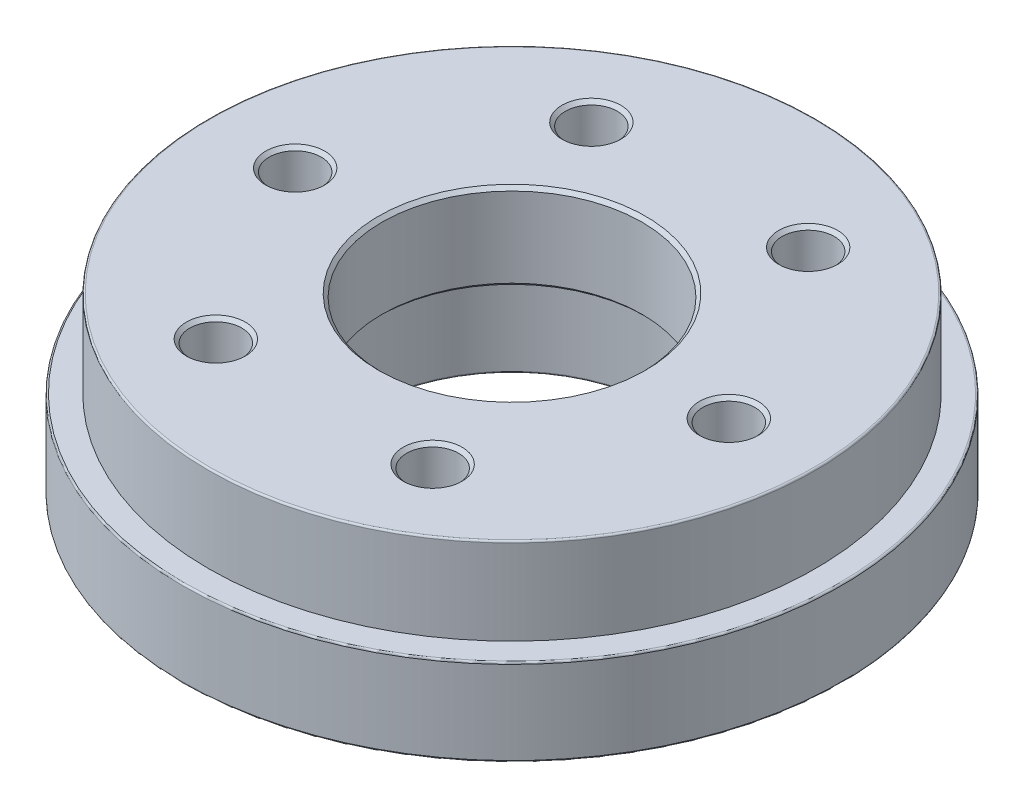
SolidWorks part; units mm, degrees
ref_plane "前视基准面" through (0, 0, 0) normal (0, 0, 1) x (1, 0, 0)
ref_plane "上视基准面" through (0, 0, 0) normal (0, 1, 0) x (1, 0, 0)
ref_plane "右视基准面" through (0, 0, 0) normal (1, 0, 0) x (0, 0, -1)
other "Configuration Table"
sketch "草图1" plane through (0, 0, 0) normal (0, 1, 0) x (1, 0, 0)
  circle A0 centre (0, 0) radius 19
  circle A1 centre (0, 0) radius 15 construction
  circle A2 centre (0, 15) radius 3.05
  circle A3 centre (12.9904, 7.5) radius 3.05
  circle A4 centre (12.9904, -7.5) radius 3.05
  circle A5 centre (0, -15) radius 3.05
  circle A6 centre (-12.9904, -7.5) radius 3.05
  circle A7 centre (-12.9904, 7.5) radius 3.05
  point P18 (0, 0)
  dimension "D1" = 6.1
  dimension "D2" = 38
  dimension "D3" = 30
  dimension "D4" = 6
extrude "凸台-拉伸1" add sketch "草图1" along normal blind 5 contours A0
extrude "切除-拉伸1" cut sketch "草图1<3>" along normal blind 4 contours A7 | A6 | A5 | A4 | A3 | A2 region at (0, 0, -15) region at (12.9904, 0, -7.5) region at (12.9904, 0, 7.5) region at (0, 0, 15) region at (-12.9904, 0, 7.5) region at (-12.9904, 0, -7.5)
sketch "草图1<3>" plane through (0, 0, 0) normal (0, 1, 0) x (1, 0, 0) same geometry as "草图1"
sketch "草图5" plane through (0, 5, 0) normal (0, 1, 0) x (1, 0, 0)
  circle A1 centre (0, 0) radius 17.5
  dimension "D1" = 35
extrude "凸台-拉伸3" add sketch "草图5" along normal blind 5
sketch "草图7" plane through (0, 0, 0) normal (0, -1, 0) x (1, 0, 0)
  circle A0 centre (0, 0) radius 8.5
  dimension "D1" = 17
extrude "切除-拉伸2" cut sketch "草图7" against normal blind 5
sketch "草图8" plane through (0, 5, 0) normal (0, -1, 0) x (1, 0, 0)
  circle A0 centre (0, 0) radius 7.5
  dimension "D1" = 15
extrude "切除-拉伸3" cut sketch "草图8" against normal blind 0.5
sketch "草图10" plane through (0, 0, 0) normal (0, -1, 0) x (1, 0, 0)
  line L0 (0, 15) -> (12.9904, 7.5) construction
  line L2 (6.25, 10.8253) -> (0, 0) construction
  circle A0 centre (0, 0) radius 12.5 construction
  circle A1 centre (6.25, 10.8253) radius 1.5
  circle A2 centre (12.5, 0) radius 1.5
  circle A3 centre (6.25, -10.8253) radius 1.5
  circle A4 centre (-6.25, -10.8253) radius 1.5
  circle A5 centre (-12.5, 0) radius 1.5
  circle A6 centre (-6.25, 10.8253) radius 1.5
  point P21 (0, 0)
  dimension "D1" = 3
  dimension "D3" = 25
  dimension "D2" = 6
extrude "切除-拉伸4" cut sketch "草图10" against normal up to next
sketch "草图11" plane through (0, 0, 0) normal (0, -1, 0) x (1, 0, 0)
  line L0 (6.25, -14.0007) -> (9, -12.413)
  line L1 (15.25, -1.5877) -> (15.25, 1.5877)
  line L2 (15.25, 1.5877) -> (12.5, 3.1754)
  line L3 (12.5, 3.1754) -> (9.75, 1.5877)
  line L4 (9.75, 1.5877) -> (9.75, -1.5877)
  line L5 (9.75, -1.5877) -> (12.5, -3.1754)
  line L6 (12.5, -3.1754) -> (15.25, -1.5877)
  line L7 (9, -12.413) -> (9, -9.2376)
  line L8 (9, -9.2376) -> (6.25, -7.6499)
  line L9 (6.25, -7.6499) -> (3.5, -9.2376)
  line L10 (3.5, -9.2376) -> (3.5, -12.413)
  line L11 (3.5, -12.413) -> (6.25, -14.0007)
  line L12 (-9, -12.413) -> (-6.25, -14.0007)
  line L13 (-6.25, -14.0007) -> (-3.5, -12.413)
  line L14 (-3.5, -12.413) -> (-3.5, -9.2376)
  line L15 (-3.5, -9.2376) -> (-6.25, -7.6499)
  line L16 (-6.25, -7.6499) -> (-9, -9.2376)
  line L17 (-9, -9.2376) -> (-9, -12.413)
  line L18 (-15.25, 1.5877) -> (-15.25, -1.5877)
  line L19 (-15.25, -1.5877) -> (-12.5, -3.1754)
  line L20 (-12.5, -3.1754) -> (-9.75, -1.5877)
  line L21 (-9.75, -1.5877) -> (-9.75, 1.5877)
  line L22 (-9.75, 1.5877) -> (-12.5, 3.1754)
  line L23 (-12.5, 3.1754) -> (-15.25, 1.5877)
  line L24 (-6.25, 14.0007) -> (-9, 12.413)
  line L25 (-9, 12.413) -> (-9, 9.2376)
  line L26 (-9, 9.2376) -> (-6.25, 7.6499)
  line L27 (-6.25, 7.6499) -> (-3.5, 9.2376)
  line L28 (-3.5, 9.2376) -> (-3.5, 12.413)
  line L29 (-3.5, 12.413) -> (-6.25, 14.0007)
  line L30 (9, 12.413) -> (6.25, 14.0007)
  line L31 (6.25, 14.0007) -> (3.5, 12.413)
  line L32 (3.5, 12.413) -> (3.5, 9.2376)
  line L33 (3.5, 9.2376) -> (6.25, 7.6499)
  line L34 (6.25, 7.6499) -> (9, 9.2376)
  line L35 (9, 9.2376) -> (9, 12.413)
  circle A0 centre (12.5, 0) radius 2.75 construction
  point P41 (0, 0)
  dimension "D1" = 5.5
  dimension "D2" = 6
extrude "切除-拉伸5" cut sketch "草图11" against normal blind 2
sketch "草图12" plane through (0, 10, 0) normal (0, 1, 0) x (1, 0, 0)
  circle A0 centre (0, 0) radius 7.5
  dimension "D1" = 15
extrude "切除-拉伸6" cut sketch "草图12" against normal up to next
chamfer "倒角1" distance 0.2 angle 45 14 edges at (-12.5, 2, -1.5) (-12.5, 10, 1.5) (-6.25, 2, 9.3253) (-6.25, 10, 12.3253) (6.25, 2, 9.3253) (6.25, 10, 12.3253) (12.5, 2, -1.5) (12.5, 10, 1.5) (6.25, 2, -12.3253) (6.25, 10, -9.3253) (-6.25, 2, -12.3253) (-6.25, 10, -9.3253) (0, 10, 7.5) (0, 5, -7.5)
fillet "圆角1" radius 0.1 4 edges at (0, 0, 19) (0, 5, 19) (0, 0, -8.5) (0, 10, 17.5)
fillet "圆角2" radius 0.1 6 edges at (12.9904, 0, 10.55) (12.9904, 0, -4.45) (0, 0, -11.95) (-12.9904, 0, -4.45) (-12.9904, 0, 10.55) (0, 0, 18.05)
